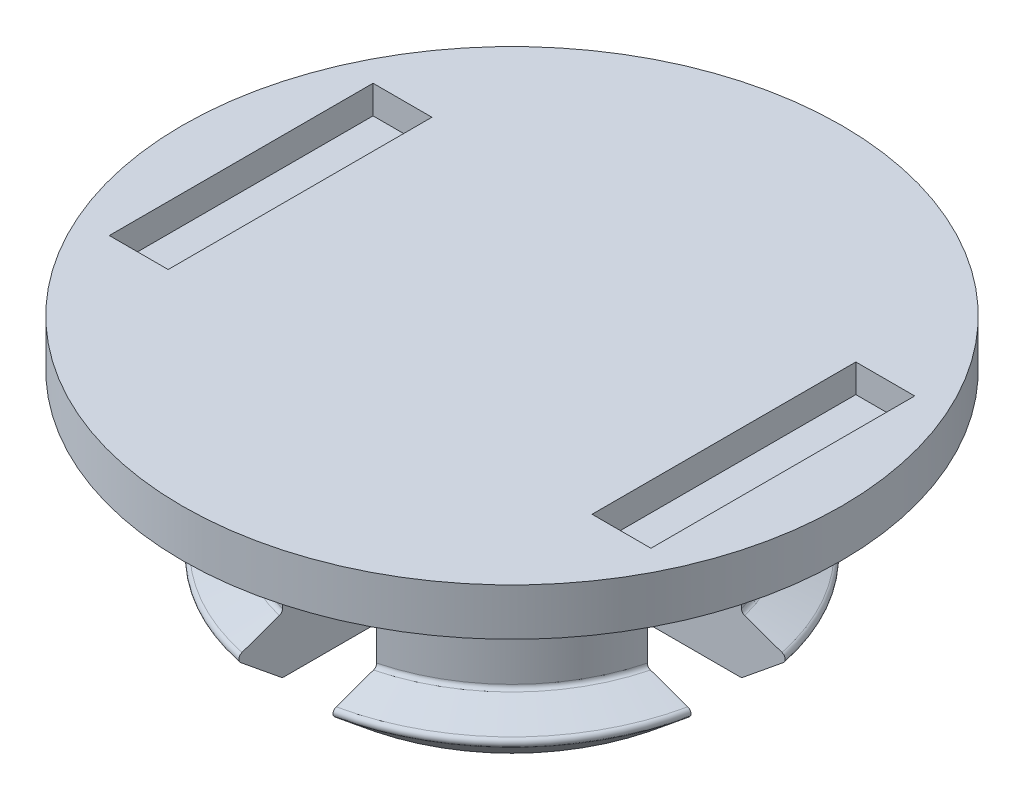
SolidWorks part; units mm, degrees
ref_plane "Front Plane" through (0, 0, 0) normal (0, 0, 1) x (1, 0, 0)
ref_plane "Top Plane" through (0, 0, 0) normal (0, 1, 0) x (1, 0, 0)
ref_plane "Right Plane" through (0, 0, 0) normal (1, 0, 0) x (0, 0, -1)
sketch "Szkic1" plane through (0, 0, 0) normal (0, 1, 0) x (1, 0, 0)
  circle A0 centre (0, 0) radius 7
  dimension "D1" = 14
extrude "Dodanie-wyciągnięcie1" add sketch "Szkic1" along normal blind 1
ref_point "Punkt1"
ref_plane "Płaszczyzna1" through (0, 0, 0) normal (0, -1, 0) x (-1, 0, 0)
sketch "Szkic2" plane through (0, 0, 0) normal (0, -1, 0) x (-1, 0, 0)
  circle A0 centre (0, 0) radius 4
  dimension "D1" = 8
extrude "Dodanie-wyciągnięcie2" add sketch "Szkic2" along normal blind 4.22
ref_axis "Oś1" through (0, -4.22, 0) along (0, 1, 0)
sketch "Szkic3" plane through (0, 0, 0) normal (1, 0, 0) x (0, 0, -1)
  line L1 (4, -4.22) -> (5, -3.384)
  line L2 (5, -3.384) -> (4, -3.02)
  line L4 (4, -3.02) -> (4, -4.22)
  line L5 (0, -4.22) -> (0, 0) construction
  line L7 (-7.7, 0) -> (7.7, 0) construction
  point P4 (3.9272, -4.22)
  dimension "D1" = 4
  dimension "D2" = 1.2
  dimension "D3" = 70
  dimension "D4" = 4.22
  dimension "D5" = 5
revolve "Obrót1" add sketch "Szkic3" angle 360 about axis through (0, -4.22, 0) along (0, 1, 0)
fillet "Zaokrąglenie1" radius 0.1 3 edges at (0, -3.384, -5) (0, -3.02, -4) (0, -4.22, -4)
ref_plane "Płaszczyzna2" through (0, -4.22, 0) normal (0, -1, 0) x (-1, 0, 0)
sketch "Szkic5" plane through (0, -4.22, 0) normal (0, -1, 0) x (-1, 0, 0)
  line L0 (-7.7941, -1) -> (-1, -1)
  line L1 (7.7941, 1) -> (1, 1)
  line L2 (-1, -7.7941) -> (-1, -1)
  line L3 (1, 7.7941) -> (1, 1)
  line L4 (-1, 1) -> (-1, 7.7941)
  line L5 (1, -1) -> (7.7941, -1)
  line L6 (1, -1) -> (1, -7.7941)
  line L7 (-1, 1) -> (-7.7941, 1)
  line L8 (-1, -1) -> (1, 1) construction
  arc A0 (-7.7941, 1) -> (-7.7941, -1) centre (0, 0) ccw
  arc A1 (-1, -7.7941) -> (1, -7.7941) centre (0, 0) ccw
  arc A2 (7.7941, -1) -> (7.7941, 1) centre (0, 0) ccw
  arc A3 (1, 7.7941) -> (-1, 7.7941) centre (0, 0) ccw
  point P1 (0, 0)
  dimension "D1" = 2
  dimension "D2" = 2
extrude "Wytnij-wyciągnięcie1" cut sketch "Szkic5" against normal blind 4.22
ref_plane "Płaszczyzna3" through (0, 1, 0) normal (0, 1, 0) x (1, 0, 0)
sketch "Szkic8" plane through (0, 1, 0) normal (0, 1, 0) x (1, 0, 0)
  line L0 (4.5, -2.8) -> (-4.5, 2.8) construction
  line L1 (5.75, -2.8) -> (4.5, -2.8)
  line L2 (5.75, -2.8) -> (5.75, 2.8)
  line L3 (5.75, 2.8) -> (4.5, 2.8)
  line L4 (4.5, -2.8) -> (4.5, 2.8)
  line L5 (-4.5, -2.8) -> (-5.75, -2.8)
  line L6 (-4.5, -2.8) -> (-4.5, 2.8)
  line L7 (-4.5, 2.8) -> (-5.75, 2.8)
  line L8 (-5.75, -2.8) -> (-5.75, 2.8)
  point P8 (0, 0)
  point P9 (0, 0)
  dimension "D1" = 5.6
  dimension "D2" = 1.25
  dimension "D3" = 9
extrude "Wytnij-wyciągnięcie2" cut sketch "Szkic8" against normal blind 0.6
